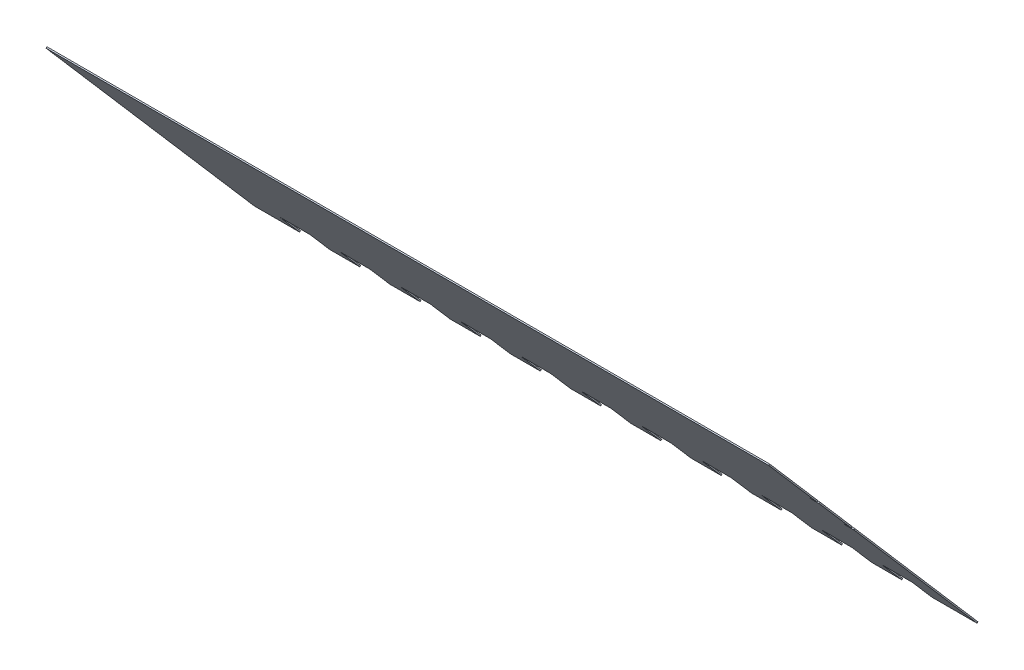
SolidWorks part; units mm, degrees
note: The reader was unsure of these and kept them because the rebuilt part matched: thickness of "Base-Flange1", "Sheet-Metal1", "Sheet-Metal2", "Sheet-Metal3".
material "AISI 304"
ref_plane "Front Plane" through (0, 0, 0) normal (0, 0, 1) x (1, 0, 0)
ref_plane "Top Plane" through (0, 0, 0) normal (0, 1, 0) x (1, 0, 0)
ref_plane "Right Plane" through (0, 0, 0) normal (1, 0, 0) x (0, 0, -1)
sketch "Sketch1" plane through (0, 0, 0) normal (1, 0, 0) x (0, 0, -1)
  line L0 (0, 0) -> (346, -400)
  line L1 (0, 0) -> (-200, 0) construction
  line L2 (346, -400) -> (-200, -400) construction
  line L3 (-200, -400) -> (-200, 0) construction
  dimension "D3" = 400
  dimension "D1" = 200
  dimension "D2" = 546
base flange "Base-Flange1" sketch "Sketch1" end condition mid plane depth 1200 reverse direction yes thickness 2 reverse thickness direction no bend radius 0.7366
sketch "Sketch2" plane through (0, 0, 0) normal (0, 0.6542, -0.7563) x (-1, 0, 0)
  line L0 (600, -528.8818) -> (-600, -528.8818) construction
  line L1 (-525, -528.8818) -> (-475, -528.8818)
  line L2 (-525, -528.8818) -> (-525, -478.8818)
  line L3 (-525, -478.8818) -> (-475, -478.8818)
  line L4 (-475, -528.8818) -> (-475, -478.8818)
  line L6 (-425, -528.8818) -> (-425, -478.8818)
  line L7 (-425, -528.8818) -> (-375, -528.8818)
  line L8 (-375, -528.8818) -> (-375, -478.8818)
  line L9 (-425, -478.8818) -> (-375, -478.8818)
  line L10 (-325, -528.8818) -> (-325, -478.8818)
  line L11 (-325, -528.8818) -> (-275, -528.8818)
  line L12 (-275, -528.8818) -> (-275, -478.8818)
  line L13 (-325, -478.8818) -> (-275, -478.8818)
  line L14 (-225, -528.8818) -> (-225, -478.8818)
  line L15 (-225, -528.8818) -> (-175, -528.8818)
  line L16 (-175, -528.8818) -> (-175, -478.8818)
  line L17 (-225, -478.8818) -> (-175, -478.8818)
  line L18 (-125, -528.8818) -> (-125, -478.8818)
  line L19 (-125, -528.8818) -> (-75, -528.8818)
  line L20 (-75, -528.8818) -> (-75, -478.8818)
  line L21 (-125, -478.8818) -> (-75, -478.8818)
  line L22 (-25, -528.8818) -> (-25, -478.8818)
  line L23 (-25, -528.8818) -> (25, -528.8818)
  line L24 (25, -528.8818) -> (25, -478.8818)
  line L25 (-25, -478.8818) -> (25, -478.8818)
  line L26 (75, -528.8818) -> (75, -478.8818)
  line L27 (75, -528.8818) -> (125, -528.8818)
  line L28 (125, -528.8818) -> (125, -478.8818)
  line L29 (75, -478.8818) -> (125, -478.8818)
  line L30 (175, -528.8818) -> (175, -478.8818)
  line L31 (175, -528.8818) -> (225, -528.8818)
  line L32 (225, -528.8818) -> (225, -478.8818)
  line L33 (175, -478.8818) -> (225, -478.8818)
  line L34 (275, -528.8818) -> (275, -478.8818)
  line L35 (275, -528.8818) -> (325, -528.8818)
  line L36 (325, -528.8818) -> (325, -478.8818)
  line L37 (275, -478.8818) -> (325, -478.8818)
  line L38 (375, -528.8818) -> (375, -478.8818)
  line L39 (375, -528.8818) -> (425, -528.8818)
  line L40 (425, -528.8818) -> (425, -478.8818)
  line L41 (375, -478.8818) -> (425, -478.8818)
  line L74 (-600, -528.8818) -> (-525, -528.8818) construction
  line L75 (600, -528.8818) -> (525, -528.8818) construction
  line L76 (475, -528.8818) -> (475, -478.8818)
  line L77 (475, -528.8818) -> (525, -528.8818)
  line L78 (525, -528.8818) -> (525, -478.8818)
  line L79 (475, -478.8818) -> (525, -478.8818)
  dimension "D1" = 50
  dimension "D2" = 50
  dimension "D3" = 50
  dimension "D4" = 11
extrude "Cut-Extrude1" cut sketch "Sketch2" against normal blind 10
sketch "Sketch3" plane through (600, 0, 0) normal (1, 0, 0) x (0, 0, -1)
  line L0 (136.9349, -158.3063) -> (135.4223, -159.6147)
  line L1 (0, 0) -> (346, -400) construction
  line L2 (-1.5126, -1.3084) -> (344.4874, -401.3084) construction
  line L3 (135.4223, -159.6147) -> (140.0018, -164.9089)
  line L4 (140.0018, -164.9089) -> (141.5144, -163.6005)
  line L5 (0, 0) -> (346, -400) construction
  line L6 (141.5144, -163.6005) -> (136.9349, -158.3063)
  line L7 (80.9059, -93.5328) -> (83.543, -96.5815)
  line L8 (83.543, -96.5815) -> (82.0304, -97.8899)
  line L9 (82.0304, -97.8899) -> (79.3932, -94.8412)
  line L10 (79.3932, -94.8412) -> (80.9059, -93.5328)
  dimension "D1" = 7
  dimension "D2" = 4.031
extrude "Cut-Extrude2" cut sketch "Sketch3" against normal blind 13 normal cut yes
fillet "Fillet1" radius 0.74 2 edges at (600, -164.2547, -140.7581) (600, -94.187, -80.1496)
sketch "Bend-Lines1" [suppressed] plane through (0, 0, 0) normal (0, 1, 0) x (1, 0, 0)
sketch "Bounding-Box1" [suppressed] plane through (0, 0, 0) normal (0, 1, 0) x (1, 0, 0)
sheet metal parameters "Sheet-Metal1" thickness 2 parameters "D1"=0.7366
flat pattern "Flat-Pattern1" [suppressed]
sketch "Bend-Lines2" plane through (0, 0, 0) normal (0, 1, 0) x (1, 0, 0)
sketch3d "Bounding-Box2" [suppressed]
  line L0 (-1200, -528.8818, 0) -> (0, -528.8818, 0) construction
  line L1 (-1200, 0, 0) -> (0, 0, 0) construction
  line L2 (-1200, -528.8818, 0) -> (-1200, 0, 0) construction
  line L3 (0, -528.8818, 0) -> (0, 0, 0) construction
sheet metal parameters "Sheet-Metal2" thickness 2 parameters "D1"=0.7366
flat pattern "Flat-Pattern1"
sketch "Bend-Lines2" plane through (0, 0, 0) normal (0, 1, 0) x (1, 0, 0)
sketch3d "Bounding-Box2" [suppressed]
  line L0 (-1200, -528.8818, 0) -> (0, -528.8818, 0) construction
  line L1 (-1200, 0, 0) -> (0, 0, 0) construction
  line L2 (-1200, -528.8818, 0) -> (-1200, 0, 0) construction
  line L3 (0, -528.8818, 0) -> (0, 0, 0) construction
sheet metal parameters "Sheet-Metal3" thickness 2 parameters "D1"=0.7366
flat pattern "Flat-Pattern1"
sketch "Bend-Lines2" plane through (0, 0, 0) normal (0, 1, 0) x (1, 0, 0)
sketch3d "Bounding-Box2" [suppressed]
  line L0 (-1200, -528.8818, 0) -> (0, -528.8818, 0) construction
  line L1 (-1200, 0, 0) -> (0, 0, 0) construction
  line L2 (-1200, -528.8818, 0) -> (-1200, 0, 0) construction
  line L3 (0, -528.8818, 0) -> (0, 0, 0) construction
equation "\"thickness 1\" = 2"
equation "\"thickness 2\"= 3"
equation "\"connecting flange\"= 35"
equation "\"main length\"= 1200"
equation "\"main width\"= 1200"
equation "\"divider panel distance offset\"= 296"
equation "\"access hatch length\" = \"access hatch cutout length\" + \"access hatch offset\" * 2"
equation "\"access hatch width\" = \"access hatch cutout width\" + \"access hatch offset\" * 2"
equation "\"side panel length\"= 1200"
equation "\"side panel width\"= 950"
equation "\"drift eliminator size offset\"= 5"
equation "\"drift eliminator depth\" = \"divider panel distance offset\""
equation "\"D2@Base-Flange1\"=\"main width\""
equation "\"D7@Sheet-Metal1\"=\"thickness 1\""
equation "\"slotted panel length\" = \"main length\" + 100"
equation "\"slotted panel width\" = \"main width\""
equation "\"slot count x\"= 4"
equation "\"slot count y\"= 9"
equation "\"slot offset\" = \"water tray depth\""
equation "\"slot length\"= 30"
equation "\"slot width\"= 200"
equation "\"slot offset x\" = \"slot length\" + \"slot offset\""
equation "\"slot offset y\" = \"slot width\" + \"slot offset\""
equation "\"guide rail flange\"= 40"
equation "\"guid rail flange mount side\"= 20"
equation "\"guid rail back length\" = \"main width\" - \"guide rail flange\" * 2"
equation "\"splash plate width\" = \"main width\""
equation "\"dimpled panel length\" = \"main length\" - 200 - \"water tray depth\"/2"
equation "\"dimpled panel top offset\" = \"water tray depth\"/2"
equation "\"dimpled panel width\" = \"main width\""
equation "\"D3@Sketch1\"=\"splash plate length\""
equation "\"splash plate length\"= 400"
equation "\"splash plate air gap\"= 200"
equation "\"splash plate slot count\"= 11"
equation "\"splash plate slot length\"= 50"
equation "\"splash plate slot height\"= 50"
equation "\"splash plate slot offset\"= 65"
equation "\"water tray depth\"= 150"
equation "\"water tray width\"= 200"
equation "\"dimple panel slot count\"= 36"
equation "\"dimple panel slot length\"= 8"
equation "\"dimple panel slot width\"= 8"
equation "\"dimple panel slot offset\"= 25"
equation "\"D1@Sketch1\"=\"splash plate air gap\""
equation "\"D1@Sketch2\"=\"splash plate slot length\""
equation "\"D2@Sketch2\"=\"splash plate slot height\""
equation "\"D4@Sketch2\"=\"splash plate slot count\""
equation "\"D3@Sketch2\"=\"splash plate slot length\""
equation "\"thickness radius 1\"= 3.7366"
equation "\"thickness 3\"= 1.2"
equation "\"thichness 4\"= 0.8"
equation "\"connecting flange holes\"= 8"
equation "\"connecting flange hole gap\"= 100"
equation "\"cut out flange\"= 15"
equation "\"top panel slot length\"= 250"
equation "\"top panel slot width\"= 700"
equation "\"access hatch flange\" = 8 "
equation "\"access hatch cutout length\"= 400"
equation "\"access hatch cutout width\"= 600"
equation "\"access hatch cutout offset X\"= 100"
equation "\"access hatch cutout offset Y\"= 100"
equation "\"access hatch offset\"= 90"
equation "\"access hatch hole\"= 9"
equation "\"access hatch hole x gap\"= 350"
equation "\"access hatch hole y gap\"= 200"
equation "\"slot offset bottom\" = 200"
equation "\"drift eliminator cutout width\" = 1140"
equation "\"drift eliminator cutout length\" = 154"
equation "\"drift eliminator access hatch offset\" = 30"
equation "\"drift eliminator access hatch width\" = \"drift eliminator cutout width\" + \"drift eliminator access hatch offset\" * 2"
equation "\"drift eliminator access hatch length\" = \"drift eliminator cutout length\" + \"drift eliminator access hatch offset\" * 2"
equation "\"water tray panel length\"= 473"
equation "\"sump base flat section width\"= 300"
equation "\"sump upper depth\"= 300"
equation "\"sump depth\"= 550"
equation "\"leg length\" = \"sump depth\" + 150"
equation "\"leg width\"= 80"
equation "\"leg depth\"= 40"
equation "\"leg support plate size\" = \"leg width\" - \"thickness 2\" * 2"
equation "\"leg base plate thickness\"= 8"
equation "\"D1@Cut-Extrude2\"=\"cut out flange\" - \"thickness 1\""
